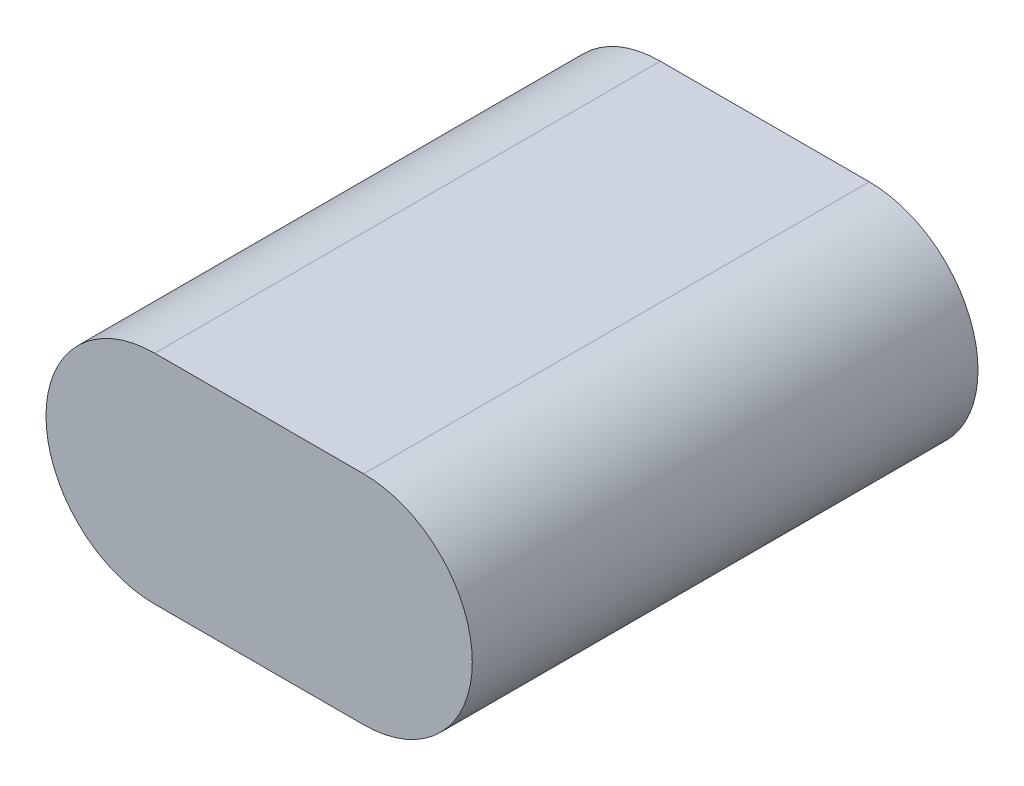
SolidWorks part; units mm, degrees
ref_plane "前视基准面" through (0, 0, 0) normal (0, 0, 1) x (1, 0, 0)
ref_plane "上视基准面" through (0, 0, 0) normal (0, 1, 0) x (1, 0, 0)
ref_plane "右视基准面" through (0, 0, 0) normal (1, 0, 0) x (0, 0, -1)
sketch "草图1" plane through (0, 0, 0) normal (0, 0, 1) x (1, 0, 0)
  line L1 (-50, 52) -> (50, 52)
  line L2 (-50, -52) -> (50, -52)
  arc A1 (-50, 52) -> (-50, -52) centre (-50, 0) ccw
  arc A2 (50, 52) -> (50, -52) centre (50, 0) cw
  point P11 (0, -52)
extrude "凸台-拉伸1" add sketch "草图1" along normal blind 242
